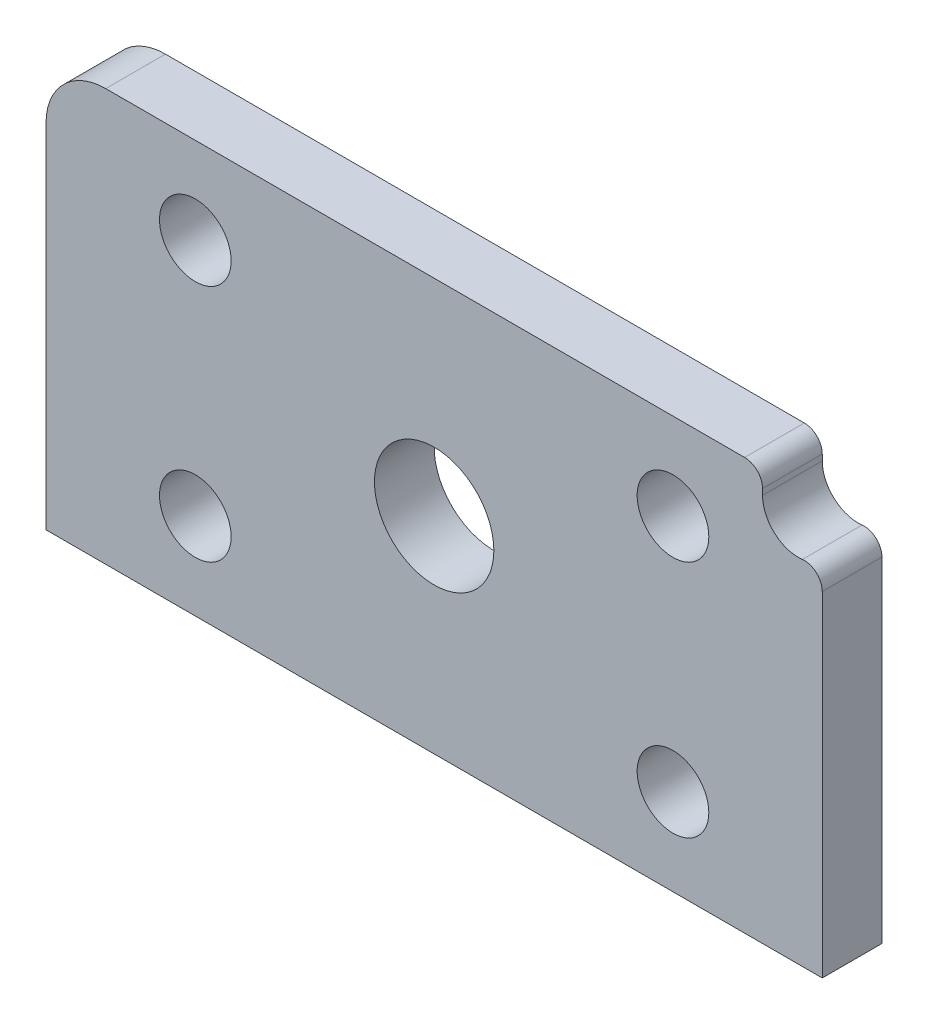
SolidWorks part; units mm, degrees
material "S355J2H"
ref_plane "Front Plane" through (0, 0, 0) normal (0, 0, 1) x (1, 0, 0)
ref_plane "Top Plane" through (0, 0, 0) normal (0, 1, 0) x (1, 0, 0)
ref_plane "Right Plane" through (0, 0, 0) normal (1, 0, 0) x (0, 0, -1)
sketch "Sketch1" plane through (0, 0, 0) normal (0, 0, 1) x (1, 0, 0)
  line L1 (-65, 34.5) -> (65, 34.5)
  line L2 (-65, 34.5) -> (-65, -34.5)
  line L3 (-65, -34.5) -> (65, -34.5)
  line L4 (65, 34.5) -> (65, -34.5)
  line L5 (-65, 34.5) -> (65, -34.5) construction
  line L6 (-65, -34.5) -> (65, 34.5) construction
  point P0 (0, 0)
  dimension "D1" = 130
  dimension "D2" = 69
base flange "Base-Flange1" sketch "Sketch1" thickness 10 reverse thickness direction no parameters "D1"=3.6
sketch "Sketch6" plane through (0, 0, 0) normal (0, 0, 1) x (1, 0, 0)
  line L1 (40, 20) -> (-40, 20) construction
  line L2 (40, 20) -> (40, -20) construction
  line L3 (40, -20) -> (-40, -20) construction
  line L4 (-40, 20) -> (-40, -20) construction
  line L5 (40, 20) -> (-40, -20) construction
  line L6 (40, -20) -> (-40, 20) construction
  circle A0 centre (0, 0) radius 10
  circle A1 centre (-40, 20) radius 6
  circle A2 centre (-40, -20) radius 6
  circle A3 centre (40, -20) radius 6
  circle A4 centre (40, 20) radius 6
  dimension "D1" = 20
  dimension "D4" = 12
  dimension "D2" = 80
  dimension "D3" = 40
extrude "Cut-Extrude1" cut sketch "Sketch6" against normal through all normal cut yes
fillet "Fillet1" radius 10 2 edges at (65, 34.5, -5) (-65, 34.5, -5)
sketch "Sketch7" plane through (0, 0, 0) normal (0, 0, 1) x (1, 0, 0)
  line L0 (61, 34.5) -> (61, 30.5) construction
  line L1 (55, 34.5) -> (-55, 34.5) construction
  line L2 (67, 34.5) -> (67, 30.5)
  line L3 (55, 34.5) -> (55, 30.5)
  line L4 (65, -34.5) -> (65, 24.5) construction
  arc A0 (67, 34.5) -> (55, 34.5) centre (61, 34.5) ccw
  arc A1 (55, 30.5) -> (67, 30.5) centre (61, 30.5) ccw
  point P4 (61, 32.5)
  dimension "D1" = 6
  dimension "D2" = 4
  dimension "D3" = 4
extrude "Cut-Extrude2" cut sketch "Sketch7" against normal through all normal cut yes
fillet "Fillet2" radius 3 2 edges at (55, 34.5, -5) (64.8962, 25.9371, -5)
sketch "Bend-Lines1" [suppressed] plane through (0, 0, 0) normal (0, 1, 0) x (1, 0, 0)
sketch "Bounding-Box1" [suppressed] plane through (0, 0, 0) normal (0, 1, 0) x (1, 0, 0)
sheet metal parameters "Sheet-Metal1" thickness 10 parameters "D1"=3.6
flat pattern "Flat-Pattern1" [suppressed]
sketch "Bend-Lines2" plane through (0, 0, 0) normal (0, 1, 0) x (1, 0, 0)
sketch3d "Bounding-Box2" [suppressed]
  line L0 (80, -34.5, 0) -> (-80, -34.5, 0) construction
  line L1 (80, 34.5, 0) -> (-80, 34.5, 0) construction
  line L2 (80, -34.5, 0) -> (80, 34.5, 0) construction
  line L3 (-80, -34.5, 0) -> (-80, 34.5, 0) construction
sheet metal parameters "Sheet-Metal2" thickness 10 parameters "D1"=3.6
flat pattern "Flat-Pattern1"
sketch "Bend-Lines2" plane through (0, 0, 0) normal (0, 1, 0) x (1, 0, 0)
sketch3d "Bounding-Box2" [suppressed]
  line L0 (-80, -34.5, 0) -> (80, -34.5, 0) construction
  line L1 (-80, 34.5, 0) -> (80, 34.5, 0) construction
  line L2 (-80, -34.5, 0) -> (-80, 34.5, 0) construction
  line L3 (80, -34.5, 0) -> (80, 34.5, 0) construction
sheet metal parameters "Sheet-Metal3" thickness 10 parameters "D1"=3.6
flat pattern "Flat-Pattern1"
sketch "Bend-Lines2" plane through (0, 0, 0) normal (0, 1, 0) x (1, 0, 0)
sketch3d "Bounding-Box2" [suppressed]
  line L0 (-65, -34.5, 0) -> (65, -34.5, 0) construction
  line L1 (-65, 34.5, 0) -> (65, 34.5, 0) construction
  line L2 (-65, -34.5, 0) -> (-65, 34.5, 0) construction
  line L3 (65, -34.5, 0) -> (65, 34.5, 0) construction
